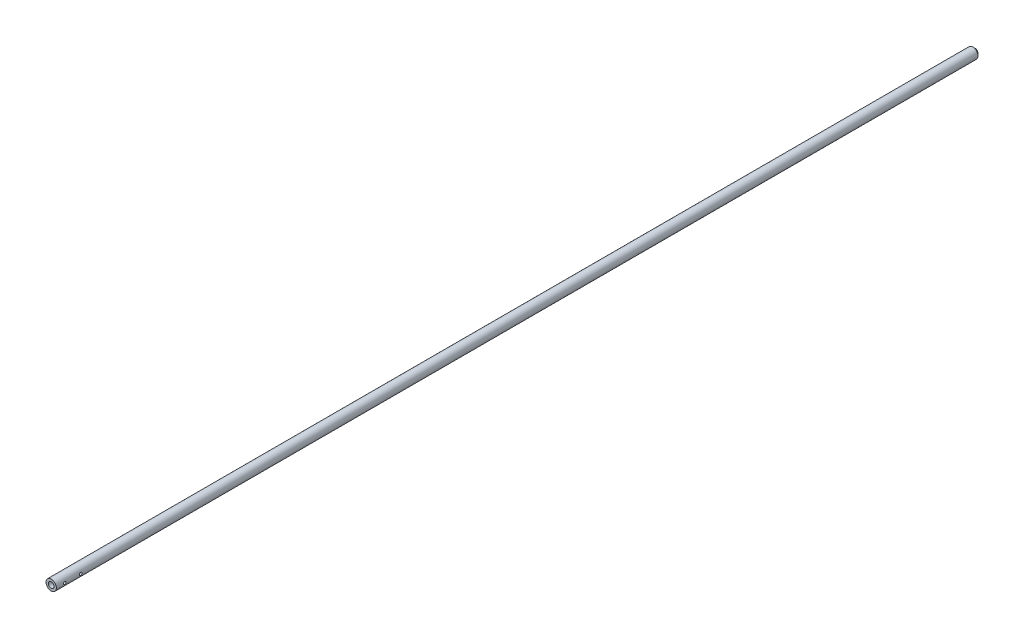
SolidWorks part; units mm, degrees
material "AISI 1035 Steel (SS)"
ref_plane "Front Plane" through (0, 0, 0) normal (0, 0, 1) x (1, 0, 0)
ref_plane "Top Plane" through (0, 0, 0) normal (0, 1, 0) x (1, 0, 0)
ref_plane "Right Plane" through (0, 0, 0) normal (1, 0, 0) x (0, 0, -1)
sketch "Sketch1" plane through (0, 0, 0) normal (0, 0, 1) x (1, 0, 0)
  circle A0 centre (0, 0) radius 1.5875
  circle A1 centre (0, 0) radius 0.8763
  dimension "D1" = 3.175
  dimension "D2" = 1.7526
extrude "Boss-Extrude1" add sketch "Sketch1" along normal blind 282.575
sketch "Sketch3" plane through (0, 0, 0) normal (1, 0, 0) x (0, 0, -1)
  line L0 (-282.575, 1.5875) -> (-282.575, -1.5875) construction
  circle A0 centre (-279.9969, 0) radius 0.3969
  circle A1 centre (-275.082, 0) radius 0.3969
  dimension "D2" = 0.7937
  dimension "D3" = 0.7937
  dimension "D1" = 2.5781
  dimension "D4" = 7.493
extrude "Cut-Extrude1" cut sketch "Sketch3" against normal mid plane 4.318
chamfer "Chamfer1" distance 0.762 angle 45 1 edges at (1.5875, 0, 0)
